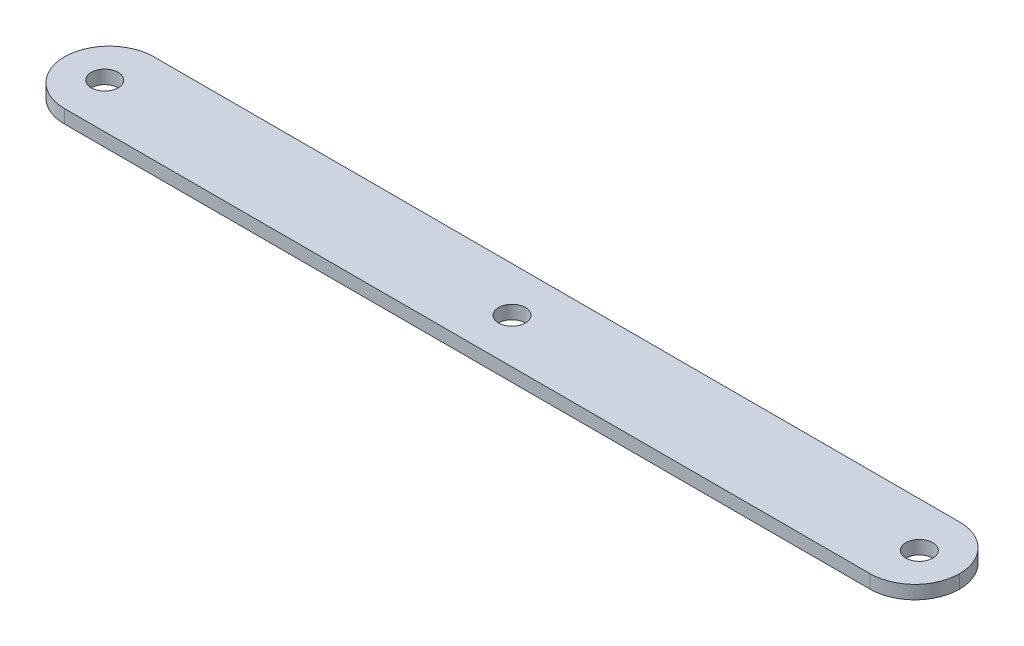
SolidWorks part; units mm, degrees
ref_plane "Front Plane" through (0, 0, 0) normal (0, 0, 1) x (1, 0, 0)
ref_plane "Top Plane" through (0, 0, 0) normal (0, 1, 0) x (1, 0, 0)
ref_plane "Right Plane" through (0, 0, 0) normal (1, 0, 0) x (0, 0, -1)
sketch "Sketch2" plane through (0, 0, 0) normal (0, 1, 0) x (1, 0, 0)
  line L1 (0, 0) -> (200, 0)
  line L2 (0, 0) -> (0, 20)
  line L3 (0, 20) -> (200, 20)
  line L4 (200, 0) -> (200, 20)
  dimension "D1" = 200
  dimension "D2" = 20
extrude "Boss-Extrude1" add sketch "Sketch2" along normal blind 3
sketch "Sketch3" plane through (0, 3, 0) normal (0, 1, 0) x (1, 0, 0)
  line L0 (200, 20) -> (0, 20) construction
  line L1 (0, 20) -> (0, 0) construction
  circle A0 centre (9, 10) radius 3
  dimension "D1" = 10
  dimension "D2" = 9
  dimension "D3" = 6
extrude "Cut-Extrude1" cut sketch "Sketch3" against normal through all
sketch "Sketch4" plane through (0, 3, 0) normal (0, 1, 0) x (1, 0, 0)
  line L0 (200, 20) -> (0, 20) construction
  line L1 (200, 0) -> (200, 20) construction
  circle A0 centre (191, 10) radius 3
  dimension "D1" = 10
  dimension "D3" = 6
  dimension "D2" = 9
extrude "Cut-Extrude2" cut sketch "Sketch4" against normal through all
fillet "Fillet1" radius 10 2 edges at (0, 1.5, -20) (0, 1.5, 0)
fillet "Fillet2" radius 10 2 edges at (200, 1.5, -20) (200, 1.5, 0)
sketch "Sketch6" plane through (0, 3, 0) normal (0, 1, 0) x (1, 0, 0)
  line L2 (190, 20) -> (10, 20) construction
  line L3 (10, 0) -> (190, 0) construction
  circle A0 centre (100, 10) radius 3
  dimension "D1" = 6
  dimension "D3" = 20
  dimension "D4" = 10
extrude "Cut-Extrude3" cut sketch "Sketch6" against normal through all
sketch "Sketch7" plane through (0, 3, 0) normal (0, 1, 0) x (1, 0, 0)
  line L0 (190, 20) -> (10, 20) construction
  line L1 (19, 15) -> (90, 15)
  line L2 (19, 15) -> (19, 5)
  line L3 (19, 5) -> (90, 5)
  line L4 (90, 15) -> (90, 5)
  line L5 (10, 0) -> (190, 0) construction
  line L7 (110, 15) -> (181, 15)
  line L8 (110, 15) -> (110, 5)
  line L9 (110, 5) -> (181, 5)
  line L10 (181, 15) -> (181, 5)
  circle A0 centre (9, 10) radius 3 construction
  circle A1 centre (100, 10) radius 3 construction
  circle A2 centre (191, 10) radius 3 construction
  dimension "D5" = 10
  dimension "D1" = 5
  dimension "D2" = 5
  dimension "D3" = 10
  dimension "D4" = 10
  dimension "D6" = 10
extrude "Cut-Extrude4" [suppressed] cut sketch "Sketch7" against normal blind 10
sketch "Sketch8" plane through (0, 3, 0) normal (0, 1, 0) x (1, 0, 0)
  line L0 (9, 10) -> (191, 10)
